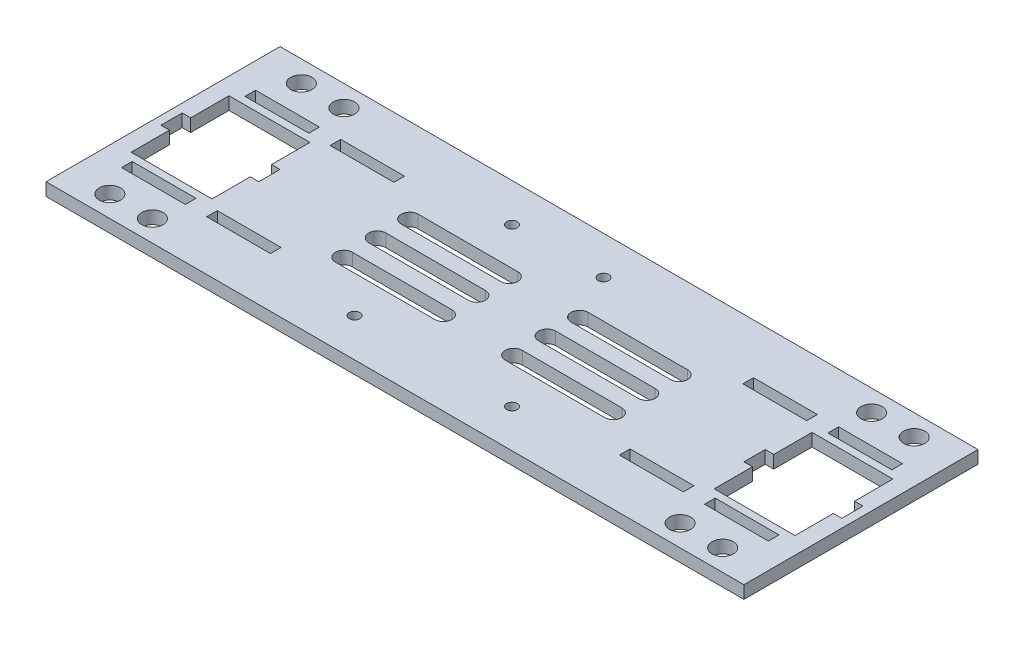
SolidWorks part; units mm, degrees
ref_plane "Front Plane" through (0, 0, 0) normal (0, 0, 1) x (1, 0, 0)
ref_plane "Top Plane" through (0, 0, 0) normal (0, 1, 0) x (1, 0, 0)
ref_plane "Right Plane" through (0, 0, 0) normal (1, 0, 0) x (0, 0, -1)
sketch "Sketch1" plane through (0, 0, 0) normal (0, 1, 0) x (1, 0, 0)
  line L0 (0, -5.7309) -> (0, 9.5321) construction
  line L1 (82, 27.5) -> (-82, 27.5)
  line L2 (82, 27.5) -> (82, -27.5)
  line L3 (82, -27.5) -> (-82, -27.5)
  line L4 (-82, 27.5) -> (-82, -27.5)
  line L5 (78, 7.2917) -> (78, -7.9583) construction
  line L6 (56, 15.75) -> (41, 15.75)
  line L7 (56, 15.75) -> (56, 13.25)
  line L8 (56, 13.25) -> (41, 13.25)
  line L9 (41, 15.75) -> (41, 13.25)
  line L10 (76, 15.75) -> (61, 15.75)
  line L11 (76, 15.75) -> (76, 13.25)
  line L12 (76, 13.25) -> (61, 13.25)
  line L13 (61, 15.75) -> (61, 13.25)
  line L14 (78, -11.5) -> (59, -11.5)
  line L15 (-7.975, 0) -> (11.9988, 0) construction
  line L16 (78, -11.5) -> (78, 11.5)
  line L17 (78, 11.5) -> (59, 11.5)
  line L18 (59, -11.5) -> (59, 11.5)
  line L19 (61, -15.75) -> (61, -13.25)
  line L20 (76, -13.25) -> (61, -13.25)
  line L21 (76, -15.75) -> (76, -13.25)
  line L22 (76, -15.75) -> (61, -15.75)
  line L23 (41, -15.75) -> (41, -13.25)
  line L24 (56, -13.25) -> (41, -13.25)
  line L25 (56, -15.75) -> (56, -13.25)
  line L26 (56, -15.75) -> (41, -15.75)
  line L27 (-78, 7.2917) -> (-78, -7.9583) construction
  line L28 (-56, -15.75) -> (-41, -15.75)
  line L29 (-56, -15.75) -> (-56, -13.25)
  line L30 (-56, -13.25) -> (-41, -13.25)
  line L31 (-41, -15.75) -> (-41, -13.25)
  line L32 (-76, -15.75) -> (-61, -15.75)
  line L33 (-76, -15.75) -> (-76, -13.25)
  line L34 (-76, -13.25) -> (-61, -13.25)
  line L35 (-61, -15.75) -> (-61, -13.25)
  line L36 (-59, -11.5) -> (-59, 11.5)
  line L37 (-78, 11.5) -> (-59, 11.5)
  line L38 (-78, -11.5) -> (-78, 11.5)
  line L39 (-78, -11.5) -> (-59, -11.5)
  line L40 (-61, 15.75) -> (-61, 13.25)
  line L41 (-76, 13.25) -> (-61, 13.25)
  line L42 (-76, 15.75) -> (-76, 13.25)
  line L43 (-76, 15.75) -> (-61, 15.75)
  line L44 (-41, 15.75) -> (-41, 13.25)
  line L45 (-56, 13.25) -> (-41, 13.25)
  line L46 (-56, 15.75) -> (-56, 13.25)
  line L47 (-56, 15.75) -> (-41, 15.75)
  point P52 (78, 0)
  point P53 (59, 0)
  dimension "D3" = 1.75
  dimension "D4" = 2.5
  dimension "D5" = 15
  dimension "D6" = 15
  dimension "D7" = 2.5
  dimension "D8" = 19
  dimension "D9" = 23
  dimension "D10" = 164
  dimension "D11" = 82
  dimension "D12" = 55
  dimension "D13" = 27.5
  dimension "D14" = 2
  dimension "D18" = 27.5
  dimension "D19" = 1.75
  dimension "D20" = 2.5
  dimension "D21" = 27.5
extrude "Boss-Extrude1" add sketch "Sketch1" along normal blind 3
sketch "Sketch2" plane through (0, 3, 0) normal (0, 1, 0) x (1, 0, 0)
  line L0 (-31.6585, 2) -> (-8.2664, 2)
  line L1 (31.6585, -9.8567) -> (8.2664, -9.8567)
  line L2 (31.6585, -5.8567) -> (8.2664, -5.8567)
  line L4 (-31.6585, -2) -> (-8.2664, -2)
  line L5 (-31.6585, 9.6208) -> (-8.2664, 9.6208)
  line L6 (-31.6585, 5.6208) -> (-8.2664, 5.6208)
  line L7 (31.6585, 5.6208) -> (8.2664, 5.6208)
  line L8 (31.6585, 9.6208) -> (8.2664, 9.6208)
  line L9 (-31.6585, -5.8567) -> (-8.2664, -5.8567)
  line L10 (31.6585, -2) -> (8.2664, -2)
  line L11 (31.6585, 2) -> (8.2664, 2)
  line L12 (-31.6585, -9.8567) -> (-8.2664, -9.8567)
  line L15 (0, 0) -> (-4.1634, 0) construction
  arc A0 (31.6585, -9.8567) -> (31.6585, -5.8567) centre (31.6585, -7.8567) ccw
  arc A1 (8.2664, -5.8567) -> (8.2664, -9.8567) centre (8.2664, -7.8567) ccw
  arc A2 (-8.2664, 2) -> (-8.2664, -2) centre (-8.2664, 0) cw
  arc A3 (-31.6585, -2) -> (-31.6585, 2) centre (-31.6585, 0) cw
  arc A4 (31.6585, 5.6208) -> (31.6585, 9.6208) centre (31.6585, 7.6208) ccw
  arc A5 (8.2664, 9.6208) -> (8.2664, 5.6208) centre (8.2664, 7.6208) ccw
  arc A6 (31.6585, -2) -> (31.6585, 2) centre (31.6585, 0) ccw
  arc A7 (8.2664, 2) -> (8.2664, -2) centre (8.2664, 0) ccw
  arc A8 (-8.2664, 9.6208) -> (-8.2664, 5.6208) centre (-8.2664, 7.6208) cw
  arc A9 (-31.6585, 5.6208) -> (-31.6585, 9.6208) centre (-31.6585, 7.6208) cw
  arc A10 (-8.2664, -5.8567) -> (-8.2664, -9.8567) centre (-8.2664, -7.8567) cw
  arc A11 (-31.6585, -9.8567) -> (-31.6585, -5.8567) centre (-31.6585, -7.8567) cw
extrude "Cut-Extrude1" cut sketch "Sketch2" against normal blind 3
sketch "Sketch3" plane through (0, 3, 0) normal (0, 1, 0) x (1, 0, 0)
  circle A0 centre (18.5, -18.5) radius 1.25
  circle A1 centre (-18.5, -18.5) radius 1.25
  circle A2 centre (-18.5, 18.5) radius 1.25
  circle A3 centre (3, 18.5) radius 1.25
  dimension "D1" = 18.5
  dimension "D2" = 3
  dimension "D3" = 2.5
  dimension "D4" = 2.5
  dimension "D5" = 2.5
  dimension "D6" = 2.5
extrude "Cut-Extrude2" cut sketch "Sketch3" against normal blind 10
sketch "Sketch4" plane through (0, 3, 0) normal (0, 1, 0) x (1, 0, 0)
  line L1 (-78, -2.5) -> (-80, -2.5)
  line L2 (59, 11.5) -> (59, -11.5) construction
  line L3 (-78, 2.5) -> (-80, 2.5)
  line L4 (-80, -2.5) -> (-80, 2.5)
  line L5 (-78, 0) -> (-80, 2.5) construction
  line L6 (-78, 0) -> (-80, -2.5) construction
  line L8 (-59, -2.5) -> (-57, -2.5)
  line L9 (59, -2.5) -> (57, -2.5)
  line L10 (-59, 2.5) -> (-57, 2.5)
  line L11 (-57, -2.5) -> (-57, 2.5)
  line L12 (-59, 0) -> (-57, 2.5) construction
  line L13 (-59, 0) -> (-57, -2.5) construction
  line L14 (-59, -2.5) -> (-59, 2.5)
  line L15 (-78, 2.5) -> (-78, -2.5)
  line L16 (82, -27.5) -> (82, 27.5) construction
  line L17 (59, 2.5) -> (57, 2.5)
  line L18 (57, -2.5) -> (57, 2.5)
  line L19 (59, 0) -> (57, 2.5) construction
  line L20 (59, 0) -> (57, -2.5) construction
  line L21 (78, -11.5) -> (78, 11.5) construction
  line L22 (78, -2.5) -> (78, 2.5)
  line L23 (80, -2.5) -> (78, -2.5)
  line L24 (80, -2.5) -> (80, 2.5)
  line L25 (80, 2.5) -> (78, 2.5)
  line L26 (-82, -27.5) -> (82, -27.5) construction
  line L27 (80, -2.5) -> (78, 0) construction
  line L28 (80, 2.5) -> (78, 0) construction
  line L29 (59, -2.5) -> (59, 2.5)
  line L30 (63.8385, 0) -> (72.3938, 0) construction
  line L31 (-82, 27.5) -> (-82, -27.5) construction
  line L34 (82, 27.5) -> (-82, 27.5) construction
  circle A0 centre (72, -22.5) radius 2.5
  circle A1 centre (62, -22.5) radius 2.5
  circle A2 centre (72, 22.5) radius 2.5
  circle A3 centre (62, 22.5) radius 2.5
  circle A4 centre (-72, 22.5) radius 2.5
  circle A5 centre (-62, 22.5) radius 2.5
  circle A6 centre (-72, -22.5) radius 2.5
  circle A7 centre (-62, -22.5) radius 2.5
  point P0 (-78, 0)
  point P2 (59, 0)
  point P7 (-59, 0)
  point P15 (78, 0)
  point P24 (78, 0)
  dimension "D3" = 10
  dimension "D5" = 5
  dimension "D7" = 10
  dimension "D8" = 5
  dimension "D9" = 5
  dimension "D10" = 5
  dimension "D11" = 10
  dimension "D12" = 5
  dimension "D13" = 10
  dimension "D14" = 5
  dimension "D15" = 5
  dimension "D16" = 5
  dimension "D17" = 5
  dimension "D18" = 5
  dimension "D19" = 10
  dimension "D20" = 10
  dimension "D21" = 5
  dimension "D22" = 5
  dimension "D23" = 2
  dimension "D1" = 5
  dimension "D2" = 5
  dimension "D4" = 5
  dimension "D6" = 5
  dimension "D24" = 2
  dimension "D25" = 0
  dimension "D26" = 2
  dimension "D28" = 2
extrude "Cut-Extrude3" cut sketch "Sketch4" against normal through all
